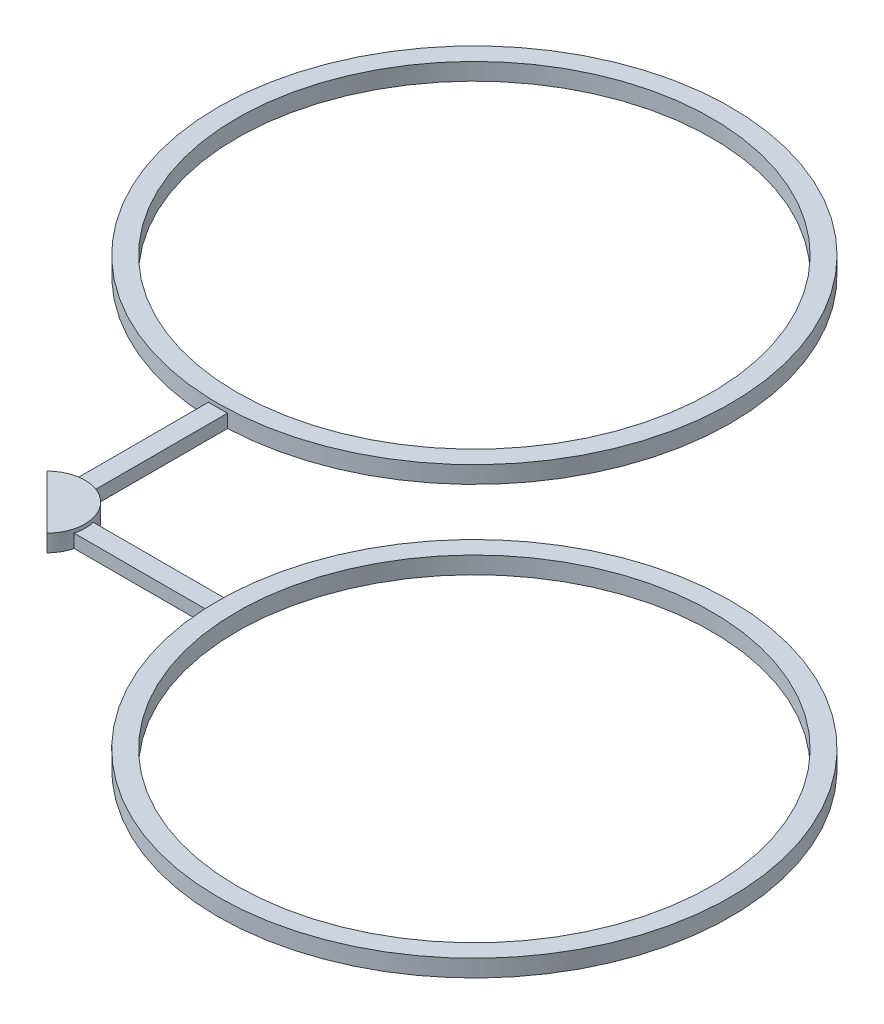
SolidWorks part; units mm, degrees
ref_plane "Front Plane" through (0, 0, 0) normal (0, 0, 1) x (1, 0, 0)
ref_plane "Top Plane" through (0, 0, 0) normal (0, 1, 0) x (1, 0, 0)
ref_plane "Right Plane" through (0, 0, 0) normal (1, 0, 0) x (0, 0, -1)
sketch "Sketch1" plane through (0, 0, 0) normal (0, 1, 0) x (1, 0, 0)
  line L0 (0, 0) -> (46.4156, 46.4156) construction
  line L1 (-2.8284, 2.8284) -> (2.8284, -2.8284)
  line L3 (-1, 18.0185) -> (-1, 3.873)
  line L5 (1, 18.0185) -> (1, 3.873)
  line L6 (-1, 10.9458) -> (1, 10.9458) construction
  line L7 (10.9458, -1) -> (10.9458, 1) construction
  line L8 (18.0185, 1) -> (3.873, 1)
  line L9 (18.0185, -1) -> (3.873, -1)
  circle A0 centre (0, 45) radius 25
  arc A1 (1, 18.0185) -> (-1, 18.0185) centre (0, 45) ccw
  arc A2 (3.873, 1) -> (1, 3.873) centre (0, 0) ccw
  arc A3 (-1, 3.873) -> (-2.8284, 2.8284) centre (0, 0) ccw
  arc A4 (3.873, -1) -> (2.8284, -2.8284) centre (0, 0) cw
  arc A5 (18.0185, 1) -> (18.0185, -1) centre (45, 0) cw
  circle A6 centre (45, 0) radius 25
  arc A7 (-1, 18.0185) -> (1, 18.0185) centre (0, 45) ccw
  arc A8 (3.873, -1) -> (3.873, 1) centre (0, 0) ccw
  arc A9 (18.0185, 1) -> (18.0185, -1) centre (45, 0) ccw
  arc A10 (-1, 3.873) -> (1, 3.873) centre (0, 0) cw
  point P13 (0, 10.9458)
  dimension "D1" = 54
  dimension "D3" = 8
  dimension "2" = 2
  dimension "D2" = 45
  dimension "D4" = 45
  dimension "D5" = 2
extrude "Boss-Extrude1" add sketch "Sketch1" along normal blind 1.8 contours A1 A7 A0 | A5 A9 A6 | A10 A3 L1 A4 A8 A2 region at (1.2004, 0, -1.2004) region at (0, 0, -71.2363) region at (18.7637, 0, 0)
extrude "Boss-Extrude2" add sketch "Sketch1<3>" along normal blind 1.4 contours L3 A10 L5 A7 | A9 L8 A8 L9 region at (0, 0, -10.982) region at (10.982, 0, 0)
sketch "Sketch1<3>" plane through (0, 0, 0) normal (0, 1, 0) x (1, 0, 0) same geometry as "Sketch1"
